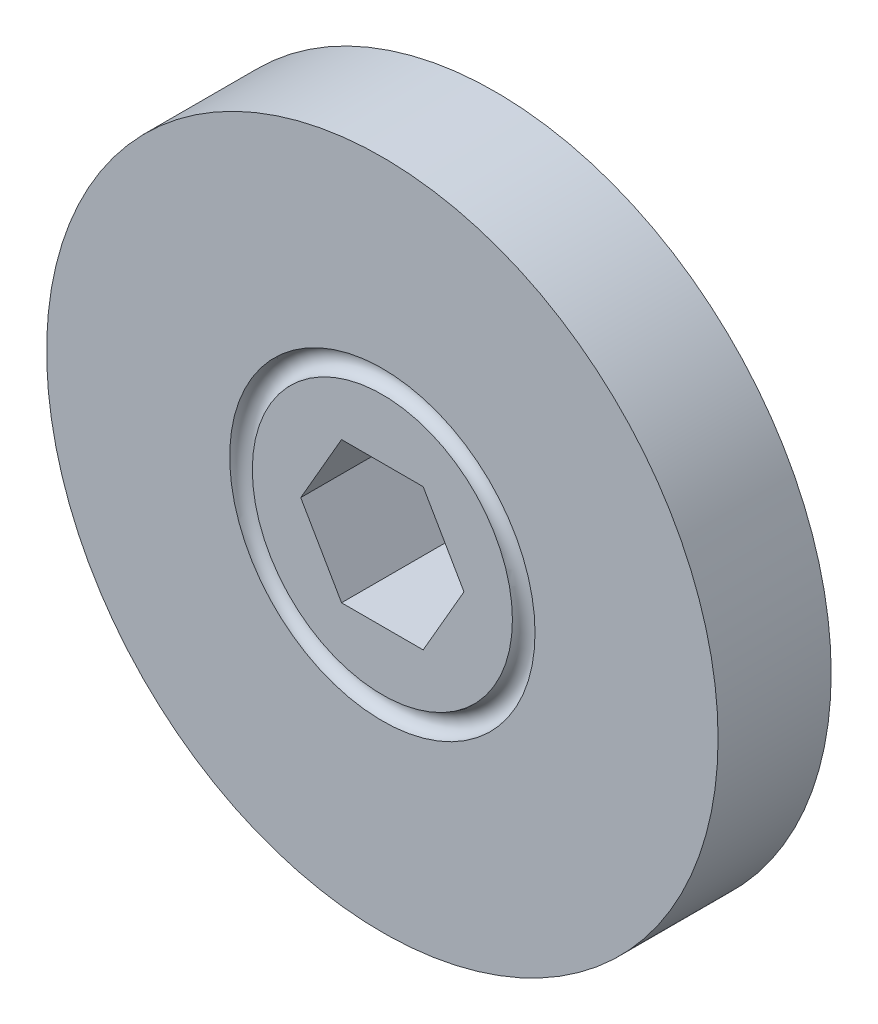
SolidWorks part; units mm, degrees
ref_plane "Front Plane" through (0, 0, 0) normal (0, 0, 1) x (1, 0, 0)
ref_plane "Top Plane" through (0, 0, 0) normal (0, 1, 0) x (1, 0, 0)
ref_plane "Right Plane" through (0, 0, 0) normal (1, 0, 0) x (0, 0, -1)
sketch "Sketch1" plane through (0, 0, 0) normal (1, 0, 0) x (0, 0, -1)
  line L0 (0, 0) -> (0, 30.1625) construction
  line L1 (-5.08, 30.1625) -> (5.08, 30.1625)
  line L2 (5.08, 30.1625) -> (5.08, 13.716)
  line L3 (5.08, 11.684) -> (5.08, 0)
  line L4 (-5.08, 11.684) -> (-5.08, 0)
  line L5 (-5.08, 30.1625) -> (-5.08, 13.716)
  line L6 (-5.08, 0) -> (5.08, 0)
  arc A0 (5.08, 13.716) -> (5.08, 11.684) centre (5.08, 12.7) ccw
  arc A1 (-5.08, 13.716) -> (-5.08, 11.684) centre (-5.08, 12.7) cw
  point P6 (0, 30.1625)
  dimension "D1" = 10.16
  dimension "D4" = 1.016
  dimension "D2" = 30.1625
  dimension "D3" = 12.7
revolve "Revolve1" add sketch "Sketch1" angle 360 about L6
sketch "Sketch2" plane through (0, 0, 5.08) normal (0, 0, 1) x (1, 0, 0)
  line L1 (-3.6662, 6.35) -> (-7.3323, 0)
  line L2 (-7.3323, 0) -> (-3.6662, -6.35)
  line L3 (-3.6662, -6.35) -> (3.6662, -6.35)
  line L4 (3.6662, -6.35) -> (7.3323, 0)
  line L5 (7.3323, 0) -> (3.6662, 6.35)
  line L6 (3.6662, 6.35) -> (-3.6662, 6.35)
  circle A0 centre (0, 0) radius 6.35 construction
  dimension "D1" = 12.7
extrude "Cut-Extrude1" cut sketch "Sketch2" against normal up to next
